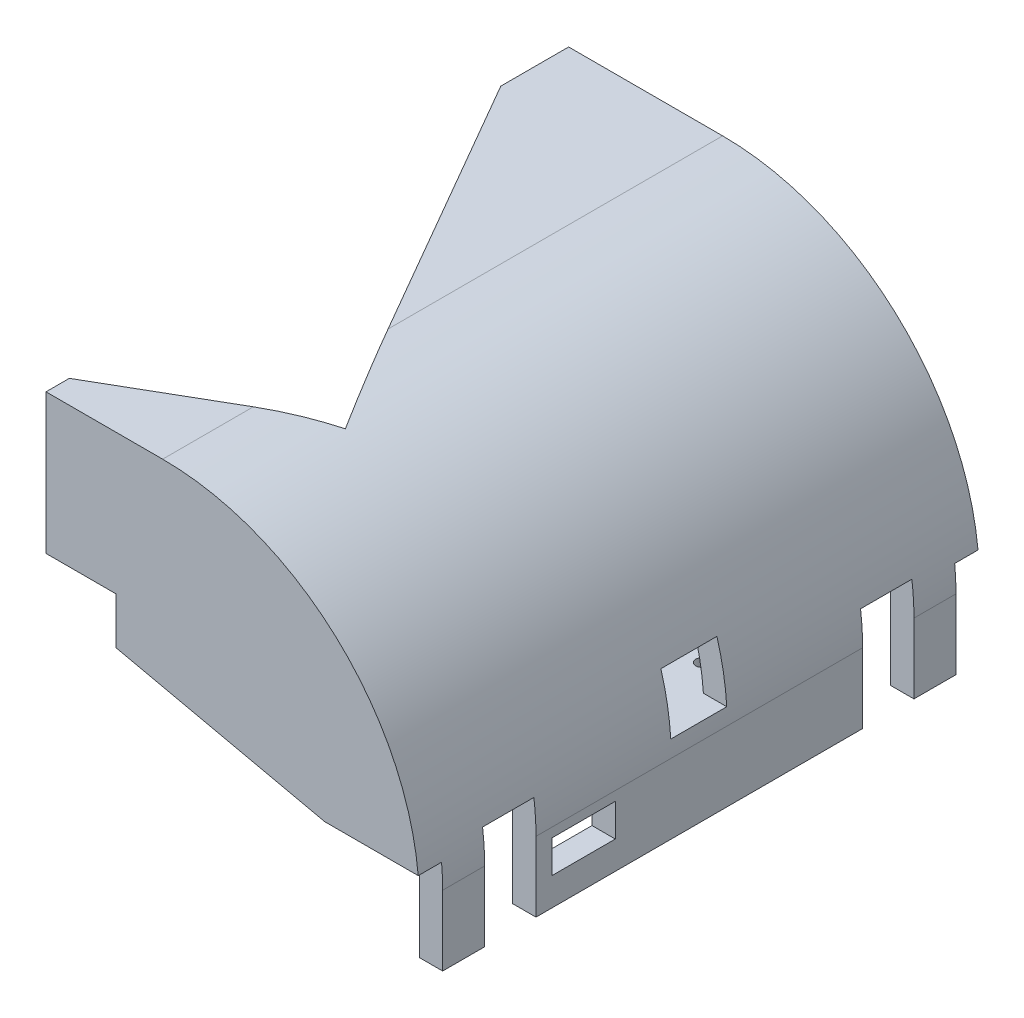
SolidWorks part; units mm, degrees
ref_plane "Front Plane" through (0, 0, 0) normal (0, 0, 1) x (1, 0, 0)
ref_plane "Top Plane" through (0, 0, 0) normal (0, 1, 0) x (1, 0, 0)
ref_plane "Right Plane" through (0, 0, 0) normal (1, 0, 0) x (0, 0, -1)
sketch "Sketch1" plane through (0, 0, 0) normal (0, 0, 1) x (1, 0, 0)
  line L1 (13.568, -0.5417) -> (18.568, -0.5417)
  line L2 (13.568, -0.5417) -> (13.568, 14.4583)
  line L3 (-36.432, 69.4583) -> (-69.432, 69.4583)
  line L4 (18.568, -0.5417) -> (18.568, 14.4583)
  line L5 (-69.432, 69.4583) -> (-69.432, 64.4583)
  line L6 (-69.432, 64.4583) -> (-36.432, 64.4583)
  arc A0 (18.568, 14.4583) -> (-36.432, 69.4583) centre (-36.432, 14.4583) ccw
  arc A1 (13.568, 14.4583) -> (-36.432, 64.4583) centre (-36.432, 14.4583) ccw
  dimension "D1" = 5
  dimension "D2" = 55
  dimension "D3" = 15
  dimension "D4" = 33
extrude "Boss-Extrude1" add sketch "Sketch1" along normal blind 110
sketch "Sketch2" plane through (13.568, 0, 0) normal (-1, 0, 0) x (0, 0, 1)
  line L0 (110, 14.4583) -> (110, -0.5417) construction
  line L1 (40, 17.9583) -> (70, 17.9583)
  line L2 (40, 17.9583) -> (40, 5.4583)
  line L3 (40, 5.4583) -> (70, 5.4583)
  line L4 (70, 17.9583) -> (70, 5.4583)
  line L6 (110, -0.5417) -> (0, -0.5417) construction
  dimension "D1" = 12.5
  dimension "D2" = 30
  dimension "D3" = 40
  dimension "D5" = 6
extrude "Boss-Extrude2" add sketch "Sketch2" along normal blind 35
sketch "Sketch3" plane through (0, 0, 40) normal (0, 0, -1) x (-1, 0, 0)
  line L0 (21.432, 5.4583) -> (-13.568, 5.4583) construction
  line L1 (-13.568, 14.4583) -> (-13.568, 5.4583) construction
  circle A0 centre (3.932, 5.4583) radius 8
  dimension "D1" = 16
  dimension "D2" = 17.5
extrude "Cut-Extrude1" cut sketch "Sketch3" against normal through all
sketch "Sketch4" plane through (0, 5.4583, 0) normal (0, -1, 0) x (1, 0, 0)
  line L0 (-21.432, 40) -> (-21.432, 70) construction
  line L2 (4.068, 70) -> (4.068, 40) construction
  line L3 (-21.432, 40) -> (-11.932, 40) construction
  line L4 (4.068, 40) -> (13.568, 40) construction
  line L5 (4.068, 70) -> (13.568, 70) construction
  line L6 (-21.432, 70) -> (-11.932, 70) construction
  circle A0 centre (-17.932, 43.5) radius 1.5
  circle A1 centre (-17.932, 66.5) radius 1.5
  circle A2 centre (7.568, 43.5) radius 1.25
  circle A3 centre (7.568, 66.5) radius 1.25
  dimension "D1" = 3
  dimension "D2" = 3
  dimension "D3" = 2.5
  dimension "D4" = 2.5
  dimension "D5" = 3.5
  dimension "D7" = 3.5
  dimension "D8" = 3.5
  dimension "D9" = 3.5
  dimension "D10" = 3.5
  dimension "D11" = 3.5
  dimension "D12" = 3.5
  dimension "D6" = 3.5
extrude "Cut-Extrude2" cut sketch "Sketch4" against normal up to surface (12.5 mm away) up to face at (-3.9933, 17.9583, 55)
sketch "Sketch5" plane through (0, 0, 40) normal (0, 0, -1) x (-1, 0, 0)
  line L1 (11.932, 5.4583) -> (21.432, 5.4583)
  line L2 (11.932, 5.4583) -> (11.932, 17.9583)
  line L3 (11.932, 17.9583) -> (21.432, 17.9583)
  line L4 (21.432, 5.4583) -> (21.432, 17.9583)
extrude "Cut-Extrude3" cut sketch "Sketch5" against normal through all
fillet "Fillet4" radius 0.5 1 edges at (-11.932, 5.4583, 55)
sketch "Sketch6" plane through (0, 0, 110) normal (0, 0, 1) x (1, 0, 0)
  line L0 (18.3325, 19.5426) -> (-1.6675, 19.5426)
  line L1 (-46.432, 29.4583) -> (-1.6675, 19.5426)
  line L3 (-69.432, 39.4583) -> (-46.432, 39.4583)
  line L5 (-69.432, 39.4583) -> (-69.432, 69.4583)
  line L6 (-69.432, 69.4583) -> (-36.432, 69.4583)
  line L7 (-46.432, 39.4583) -> (-46.432, 29.4583)
  arc A0 (18.3325, 19.5426) -> (-36.432, 69.4583) centre (-36.432, 14.4583) ccw
  arc A1 (13.568, 14.4583) -> (-36.432, 64.4583) centre (-36.432, 14.4583) ccw construction
  arc A2 (18.568, 14.4583) -> (-36.432, 69.4583) centre (-36.432, 14.4583) ccw construction
  dimension "D1" = 33
  dimension "D2" = 0
  dimension "D7" = 0
  dimension "D3" = 23
  dimension "D4" = 10
  dimension "D5" = 30
  dimension "D6" = 20
extrude "Boss-Extrude3" add sketch "Sketch6" along normal blind 5
sketch "Sketch7" plane through (13.568, 0, 0) normal (-1, 0, 0) x (0, 0, 1)
  line L0 (70, 17.9583) -> (40, 17.9583) construction
  line L1 (49, 29.9583) -> (61, 29.9583)
  line L2 (49, 29.9583) -> (49, 17.9583)
  line L3 (49, 17.9583) -> (61, 17.9583)
  line L4 (61, 29.9583) -> (61, 17.9583)
  line L5 (0, 14.4583) -> (0, -0.5417) construction
  line L6 (110, -0.5417) -> (0, -0.5417) construction
  line L7 (101, -0.5417) -> (90, -0.5417)
  line L8 (101, -0.5417) -> (101, 21.4583)
  line L9 (101, 21.4583) -> (90, 21.4583)
  line L10 (90, -0.5417) -> (90, 21.4583)
  line L11 (110, 14.4583) -> (110, -0.5417) construction
  line L12 (55, -0.5417) -> (55, 32.0893) construction
  line L13 (20, -0.5417) -> (20, 21.4583)
  line L14 (9, 21.4583) -> (20, 21.4583)
  line L15 (9, -0.5417) -> (9, 21.4583)
  line L16 (9, -0.5417) -> (20, -0.5417)
  line L17 (73, 5.4583) -> (86.6, 5.4583)
  line L18 (73, 5.4583) -> (73, 12.4583)
  line L19 (73, 12.4583) -> (86.6, 12.4583)
  line L20 (86.6, 5.4583) -> (86.6, 12.4583)
  line L21 (73, 5.4583) -> (86.6, 12.4583) construction
  line L22 (73, 12.4583) -> (86.6, 5.4583) construction
  line L23 (70, 5.4583) -> (70, 14.4583) construction
  point P4 (79.8, 8.9583)
  dimension "D1" = 12
  dimension "D2" = 12
  dimension "D3" = 49
  dimension "D4" = 9
  dimension "D5" = 11
  dimension "D6" = 22
  dimension "D7" = 13.6
  dimension "D8" = 13
  dimension "D9" = 7
  dimension "D10" = 3
  dimension "D11" = 0
extrude "Cut-Extrude4" cut sketch "Sketch7" along normal through all both and the other way through all
sketch "Sketch8" plane through (0, 0, 0) normal (0, 0, -1) x (-1, 0, 0)
  line L0 (36.432, 69.4583) -> (69.432, 69.4583)
  line L1 (69.432, 69.4583) -> (69.432, 64.4583)
  line L2 (69.432, 64.4583) -> (69.432, 39.4583)
  line L3 (46.432, 29.4583) -> (1.7077, 19.9583)
  line L4 (69.432, 39.4583) -> (46.432, 39.4583)
  line L5 (46.432, 39.4583) -> (46.432, 29.4583)
  line L6 (1.7077, 19.9583) -> (-18.2923, 19.9583)
  arc A0 (36.432, 69.4583) -> (-18.2923, 19.9583) centre (36.432, 14.4583) ccw
  dimension "D1" = 25
  dimension "D2" = 23
  dimension "D3" = 10
  dimension "D4" = 20
extrude "Boss-Extrude4" add sketch "Sketch8" along normal blind 5
sketch "Sketch10" plane through (0, 69.4583, 0) normal (0, 1, 0) x (1, 0, 0)
  line L0 (-61.432, -110) -> (-61.432, -115)
  line L1 (-69.432, -115) -> (-69.432, 5) construction
  line L2 (-23.932, -88.3494) -> (-69.432, -9.5411)
  line L4 (-36.432, -115) -> (-69.432, -115) construction
  line L5 (-61.432, -110) -> (-23.932, -88.3494)
  line L6 (-69.432, -115) -> (-69.432, -110) construction
  point P1 (-69.432, -112.5)
  dimension "D1" = 5
  dimension "D2" = 30
  dimension "D3" = 37.5
  dimension "D4" = 8
extrude "Cut-Extrude5" cut sketch "Sketch10" against normal through all and the other way through all
